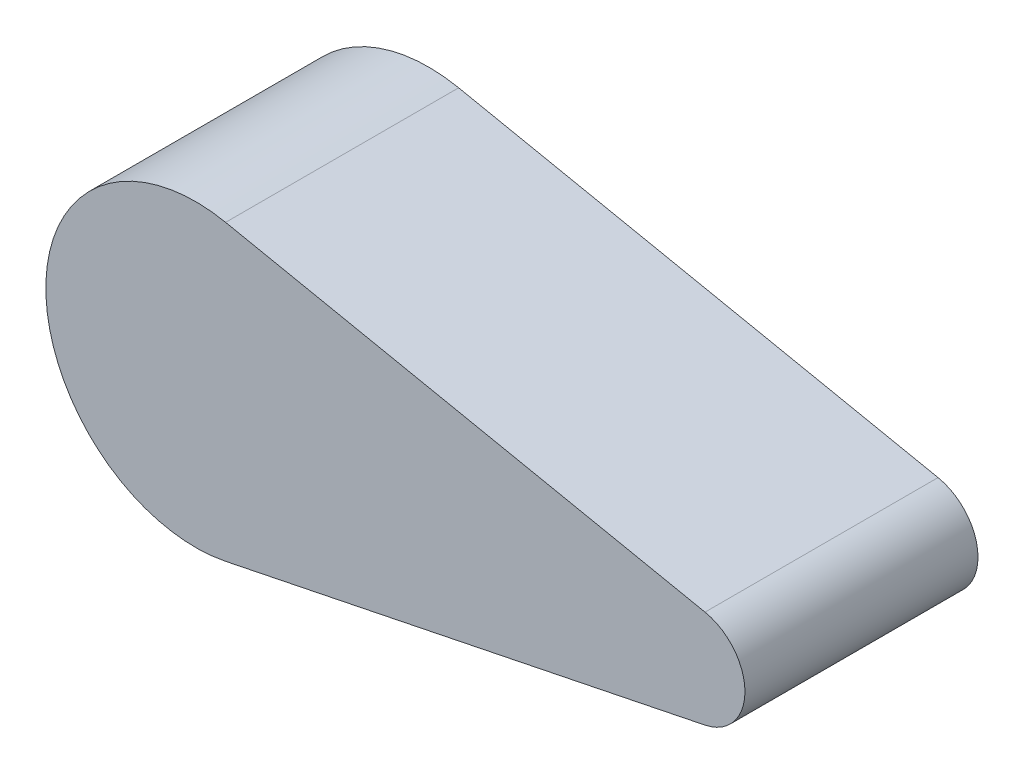
SolidWorks part; units mm, degrees
ref_plane "Front Plane" through (0, 0, 0) normal (0, 0, 1) x (1, 0, 0)
ref_plane "Top Plane" through (0, 0, 0) normal (0, 1, 0) x (1, 0, 0)
ref_plane "Right Plane" through (0, 0, 0) normal (1, 0, 0) x (0, 0, -1)
sketch "Sketch1" plane through (0, 0, 0) normal (0, 0, 1) x (1, 0, 0)
  line L0 (0, 0) -> (15, 0) construction
  line L1 (0.9, 4.4091) -> (15.3, 1.4697)
  line L2 (15.3, -1.4697) -> (0.9, -4.4091)
  arc A0 (0.9, 4.4091) -> (0.9, -4.4091) centre (0, 0) ccw
  arc A1 (15.3, -1.4697) -> (15.3, 1.4697) centre (15, 0) ccw
  dimension "D1" = 9
  dimension "D2" = 3
  dimension "D3" = 15
extrude "Boss-Extrude1" add sketch "Sketch1" along normal blind 7
sketch "Sketch2" plane through (0, 0, 0) normal (0, 0, -1) x (-1, 0, 0)
  line L20 (0.3236, -2.3303) -> (0.2859, -2.0671)
  line L21 (-0.4287, -2.0484) -> (-0.4802, -2.3093)
  line L22 (-1.1078, -2.087) -> (-0.9836, -1.8519)
  line L23 (-1.5507, -1.4168) -> (-1.7457, -1.5976)
  line L24 (-2.1228, -1.0489) -> (-1.8841, -0.9316)
  line L25 (-2.0871, -0.2463) -> (-2.3511, -0.2779)
  line L26 (-2.3337, 0.3876) -> (-2.0717, 0.3422)
  line L27 (-1.8331, 1.016) -> (-2.0653, 1.1456)
  line L28 (-1.66, 1.6737) -> (-1.4747, 1.483)
  line L29 (-0.8856, 1.8878) -> (-0.9973, 2.1292)
  line L30 (-0.359, 2.3182) -> (-0.3212, 2.055)
  line L31 (0.3934, 2.0363) -> (0.4449, 2.2972)
  line L32 (1.0724, 2.0749) -> (0.9483, 1.8398)
  line L33 (1.5153, 1.4047) -> (1.7103, 1.5854)
  line L34 (2.0874, 1.0368) -> (1.8488, 0.9195)
  line L35 (2.0518, 0.2342) -> (2.3158, 0.2658)
  line L36 (2.2983, -0.3997) -> (2.0363, -0.3543)
  line L37 (1.7977, -1.0281) -> (2.0299, -1.1577)
  line L38 (1.6246, -1.6858) -> (1.4394, -1.4951)
  line L39 (0.8503, -1.9) -> (0.962, -2.1413)
  line L40 (0.3236, -2.3303) -> (0.2859, -2.0671)
  line L41 (-0.4287, -2.0484) -> (-0.4802, -2.3093)
  line L42 (-1.1078, -2.087) -> (-0.9836, -1.8519)
  line L43 (-1.5507, -1.4168) -> (-1.7457, -1.5976)
  line L44 (-2.1228, -1.0489) -> (-1.8841, -0.9316)
  line L45 (-2.0871, -0.2463) -> (-2.3511, -0.2779)
  line L46 (-2.3337, 0.3876) -> (-2.0717, 0.3422)
  line L47 (-1.8331, 1.016) -> (-2.0653, 1.1456)
  line L48 (-1.66, 1.6737) -> (-1.4747, 1.483)
  line L49 (-0.8856, 1.8878) -> (-0.9973, 2.1292)
  line L50 (-0.359, 2.3182) -> (-0.3212, 2.055)
  line L51 (0.3934, 2.0363) -> (0.4449, 2.2972)
  line L52 (1.0724, 2.0749) -> (0.9483, 1.8398)
  line L53 (1.5153, 1.4047) -> (1.7103, 1.5854)
  line L54 (2.0874, 1.0368) -> (1.8488, 0.9195)
  line L55 (2.0518, 0.2342) -> (2.3158, 0.2658)
  line L56 (2.2983, -0.3997) -> (2.0363, -0.3543)
  line L57 (1.7977, -1.0281) -> (2.0299, -1.1577)
  line L58 (1.6246, -1.6858) -> (1.4394, -1.4951)
  line L59 (0.8503, -1.9) -> (0.962, -2.1413)
  arc A0 (-0.4287, -2.0484) -> (-0.5958, -1.7625) centre (-0.674, -2) ccw
  arc A1 (-0.6738, -1.7349) -> (-0.9836, -1.8519) centre (-0.7625, -1.9686) ccw
  arc A2 (-1.5507, -1.4168) -> (-1.5178, -1.0873) centre (-1.7206, -1.2334) ccw
  arc A3 (-1.5647, -1.0191) -> (-1.8841, -0.9316) centre (-1.7739, -1.156) ccw
  arc A4 (-2.0871, -0.2463) -> (-1.8669, 0.001) centre (-2.1169, 0.0019) ccw
  arc A5 (-1.8647, 0.0837) -> (-2.0717, 0.3422) centre (-2.1144, 0.0959) ccw
  arc A6 (-1.8331, 1.016) -> (-1.5095, 1.0866) centre (-1.7112, 1.2343) ccw
  arc A7 (-1.4592, 1.1522) -> (-1.4747, 1.483) centre (-1.654, 1.3088) ccw
  arc A8 (-0.8856, 1.8878) -> (-0.5824, 1.7548) centre (-0.6587, 1.9928) ccw
  arc A9 (-0.503, 1.7783) -> (-0.3212, 2.055) centre (-0.5687, 2.0195) ccw
  arc A10 (0.3934, 2.0363) -> (0.5605, 1.7504) centre (0.6386, 1.9879) ccw
  arc A11 (0.6385, 1.7228) -> (0.9483, 1.8398) centre (0.7272, 1.9565) ccw
  arc A12 (1.5153, 1.4047) -> (1.4825, 1.0752) centre (1.6853, 1.2213) ccw
  arc A13 (1.5294, 1.007) -> (1.8488, 0.9195) centre (1.7385, 1.1439) ccw
  arc A14 (2.0518, 0.2342) -> (1.8315, -0.0131) centre (2.0815, -0.0141) ccw
  arc A15 (1.8294, -0.0958) -> (2.0363, -0.3543) centre (2.0791, -0.108) ccw
  arc A16 (1.7977, -1.0281) -> (1.4742, -1.0987) centre (1.6759, -1.2464) ccw
  arc A17 (1.4238, -1.1643) -> (1.4394, -1.4951) centre (1.6187, -1.3209) ccw
  arc A18 (0.8503, -1.9) -> (0.5471, -1.7669) centre (0.6234, -2.005) ccw
  arc A19 (0.4677, -1.7904) -> (0.2859, -2.0671) centre (0.5333, -2.0316) ccw
  arc A20 (-0.4287, -2.0484) -> (-0.5958, -1.7625) centre (-0.674, -2) ccw
  arc A21 (-0.6738, -1.7349) -> (-0.9836, -1.8519) centre (-0.7625, -1.9686) ccw
  arc A22 (-1.5507, -1.4168) -> (-1.5178, -1.0873) centre (-1.7206, -1.2334) ccw
  arc A23 (-1.5647, -1.0191) -> (-1.8841, -0.9316) centre (-1.7739, -1.156) ccw
  arc A24 (-2.0871, -0.2463) -> (-1.8669, 0.001) centre (-2.1169, 0.0019) ccw
  arc A25 (-1.8647, 0.0837) -> (-2.0717, 0.3422) centre (-2.1144, 0.0959) ccw
  arc A26 (-1.8331, 1.016) -> (-1.5095, 1.0866) centre (-1.7112, 1.2343) ccw
  arc A27 (-1.4592, 1.1522) -> (-1.4747, 1.483) centre (-1.654, 1.3088) ccw
  arc A28 (-0.8856, 1.8878) -> (-0.5824, 1.7548) centre (-0.6587, 1.9928) ccw
  arc A29 (-0.503, 1.7783) -> (-0.3212, 2.055) centre (-0.5687, 2.0195) ccw
  arc A30 (0.3934, 2.0363) -> (0.5605, 1.7504) centre (0.6386, 1.9879) ccw
  arc A31 (0.6385, 1.7228) -> (0.9483, 1.8398) centre (0.7272, 1.9565) ccw
  arc A32 (1.5153, 1.4047) -> (1.4825, 1.0752) centre (1.6853, 1.2213) ccw
  arc A33 (1.5294, 1.007) -> (1.8488, 0.9195) centre (1.7385, 1.1439) ccw
  arc A34 (2.0518, 0.2342) -> (1.8315, -0.0131) centre (2.0815, -0.0141) ccw
  arc A35 (1.8294, -0.0958) -> (2.0363, -0.3543) centre (2.0791, -0.108) ccw
  arc A36 (1.7977, -1.0281) -> (1.4742, -1.0987) centre (1.6759, -1.2464) ccw
  arc A37 (1.4238, -1.1643) -> (1.4394, -1.4951) centre (1.6187, -1.3209) ccw
  arc A38 (0.8503, -1.9) -> (0.5471, -1.7669) centre (0.6234, -2.005) ccw
  arc A39 (0.4677, -1.7904) -> (0.2859, -2.0671) centre (0.5333, -2.0316) ccw
  ellipse E40 centre (-0.0177, -0.0061) end of major axis (-3.0095, -0.2276) minor radius 3 (-0.243, -2.9976) -> (0.0507, -3.0052) ccw
  ellipse E41 centre (-0.0177, -0.0061) end of major axis (-1.8618, -0.1426) minor radius 1.8492 (-0.6738, -1.7349) -> (-0.5958, -1.7625) ccw
  ellipse E42 centre (-0.0177, -0.0061) end of major axis (-3.0095, -0.2276) minor radius 3 (-1.9583, -2.2938) -> (-1.7253, -2.4726) ccw
  ellipse E43 centre (-0.0177, -0.0061) end of major axis (-1.8618, -0.1426) minor radius 1.8492 (-1.5647, -1.0191) -> (-1.5178, -1.0873) ccw
  ellipse E44 centre (-0.0177, -0.0061) end of major axis (-3.0095, -0.2276) minor radius 3 (-2.9324, -0.7162) -> (-2.849, -0.9979) ccw
  ellipse E45 centre (-0.0177, -0.0061) end of major axis (-1.8618, -0.1426) minor radius 1.8492 (-1.8647, 0.0837) -> (-1.8669, 0.001) ccw
  ellipse E46 centre (-0.0177, -0.0061) end of major axis (-3.0095, -0.2276) minor radius 3 (-2.7932, 1.1326) -> (-2.8912, 0.8557) ccw
  ellipse E47 centre (-0.0177, -0.0061) end of major axis (-1.8618, -0.1426) minor radius 1.8492 (-1.4592, 1.1522) -> (-1.5095, 1.0866) ccw
  ellipse E48 centre (-0.0177, -0.0061) end of major axis (-3.0095, -0.2276) minor radius 3 (-1.5938, 2.5465) -> (-1.8359, 2.3802) ccw
  ellipse E49 centre (-0.0177, -0.0061) end of major axis (-1.8618, -0.1426) minor radius 1.8492 (-0.503, 1.7783) -> (-0.5824, 1.7548) ccw
  ellipse E50 centre (-0.0177, -0.0061) end of major axis (-3.0095, -0.2276) minor radius 3 (0.2076, 2.9854) -> (-0.086, 2.9931) ccw
  ellipse E51 centre (-0.0177, -0.0061) end of major axis (-1.8618, -0.1426) minor radius 1.8492 (0.6385, 1.7228) -> (0.5605, 1.7504) ccw
  ellipse E52 centre (-0.0177, -0.0061) end of major axis (-3.0095, -0.2276) minor radius 3 (1.923, 2.2817) -> (1.6899, 2.4605) ccw
  ellipse E53 centre (-0.0177, -0.0061) end of major axis (-1.8618, -0.1426) minor radius 1.8492 (1.5294, 1.007) -> (1.4825, 1.0752) ccw
  ellipse E54 centre (-0.0177, -0.0061) end of major axis (-3.0095, -0.2276) minor radius 3 (2.8971, 0.7041) -> (2.8136, 0.9858) ccw
  ellipse E55 centre (-0.0177, -0.0061) end of major axis (-1.8618, -0.1426) minor radius 1.8492 (1.8294, -0.0958) -> (1.8315, -0.0131) ccw
  ellipse E56 centre (-0.0177, -0.0061) end of major axis (-3.0095, -0.2276) minor radius 3 (2.7578, -1.1447) -> (2.8559, -0.8679) ccw
  ellipse E57 centre (-0.0177, -0.0061) end of major axis (-1.8618, -0.1426) minor radius 1.8492 (1.4238, -1.1643) -> (1.4742, -1.0987) ccw
  ellipse E58 centre (-0.0177, -0.0061) end of major axis (-3.0095, -0.2276) minor radius 3 (1.5584, -2.5586) -> (1.8005, -2.3923) ccw
  ellipse E59 centre (-0.0177, -0.0061) end of major axis (-1.8618, -0.1426) minor radius 1.8492 (0.4677, -1.7904) -> (0.5471, -1.7669) ccw
  ellipse E60 centre (-0.0177, -0.0061) end of major axis (-3.0095, -0.2276) minor radius 3 (-0.243, -2.9976) -> (0.0507, -3.0052) ccw
  ellipse E61 centre (-0.0177, -0.0061) end of major axis (-1.8618, -0.1426) minor radius 1.8492 (-0.6738, -1.7349) -> (-0.5958, -1.7625) ccw
  ellipse E62 centre (-0.0177, -0.0061) end of major axis (-3.0095, -0.2276) minor radius 3 (-1.9583, -2.2938) -> (-1.7253, -2.4726) ccw
  ellipse E63 centre (-0.0177, -0.0061) end of major axis (-1.8618, -0.1426) minor radius 1.8492 (-1.5647, -1.0191) -> (-1.5178, -1.0873) ccw
  ellipse E64 centre (-0.0177, -0.0061) end of major axis (2.9741, 0.2155) minor radius 3 (-2.9324, -0.7162) -> (-2.849, -0.9979) ccw
  ellipse E65 centre (-0.0177, -0.0061) end of major axis (-1.8618, -0.1426) minor radius 1.8492 (-1.8647, 0.0837) -> (-1.8669, 0.001) ccw
  ellipse E66 centre (-0.0177, -0.0061) end of major axis (-3.0095, -0.2276) minor radius 3 (-2.7932, 1.1326) -> (-2.8912, 0.8557) ccw
  ellipse E67 centre (-0.0177, -0.0061) end of major axis (-1.8618, -0.1426) minor radius 1.8492 (-1.4592, 1.1522) -> (-1.5095, 1.0866) ccw
  ellipse E68 centre (-0.0177, -0.0061) end of major axis (2.9741, 0.2155) minor radius 3 (-1.5938, 2.5465) -> (-1.8359, 2.3802) ccw
  ellipse E69 centre (-0.0177, -0.0061) end of major axis (-1.8618, -0.1426) minor radius 1.8492 (-0.503, 1.7783) -> (-0.5824, 1.7548) ccw
  ellipse E70 centre (-0.0177, -0.0061) end of major axis (-3.0095, -0.2276) minor radius 3 (0.2076, 2.9854) -> (-0.086, 2.9931) ccw
  ellipse E71 centre (-0.0177, -0.0061) end of major axis (-1.8618, -0.1426) minor radius 1.8492 (0.6385, 1.7228) -> (0.5605, 1.7504) ccw
  ellipse E72 centre (-0.0177, -0.0061) end of major axis (2.9741, 0.2155) minor radius 3 (1.923, 2.2817) -> (1.6899, 2.4605) ccw
  ellipse E73 centre (-0.0177, -0.0061) end of major axis (-1.8618, -0.1426) minor radius 1.8492 (1.5294, 1.007) -> (1.4825, 1.0752) ccw
  ellipse E74 centre (-0.0177, -0.0061) end of major axis (2.9741, 0.2155) minor radius 3 (2.8971, 0.7041) -> (2.8136, 0.9858) ccw
  ellipse E75 centre (-0.0177, -0.0061) end of major axis (-1.8618, -0.1426) minor radius 1.8492 (1.8294, -0.0958) -> (1.8315, -0.0131) ccw
  ellipse E76 centre (-0.0177, -0.0061) end of major axis (-3.0095, -0.2276) minor radius 3 (2.7578, -1.1447) -> (2.8559, -0.8679) ccw
  ellipse E77 centre (-0.0177, -0.0061) end of major axis (-1.8618, -0.1426) minor radius 1.8492 (1.4238, -1.1643) -> (1.4742, -1.0987) ccw
  ellipse E78 centre (-0.0177, -0.0061) end of major axis (-3.0095, -0.2276) minor radius 3 (1.5584, -2.5586) -> (1.8005, -2.3923) ccw
  ellipse E79 centre (-0.0177, -0.0061) end of major axis (-1.8618, -0.1426) minor radius 1.8492 (0.4677, -1.7904) -> (0.5471, -1.7669) ccw
  spline S20 degree 5 poles (-1779.721, -915.2345) (7.6944, -3.6222) (-2.5035, -4.3059) (-1.1382, -4.0905) (-0.2415, -3.5081) (0.1702, -2.8271) (0.1999, -2.773) (0.226, -2.7206) (0.2478, -2.6719) (0.2651, -2.6289) (0.2798, -2.5879) (0.2923, -2.5488) (0.3031, -2.5097) (0.3107, -2.4766) (0.3176, -2.4416) (0.3448, -2.2239) (0.2959, -2.0224) (1.0633, -1.8322) (-50.4135, -4.4016) (1996.622, 113.6639) knots -4.645372 -4.645372 -4.645372 -4.645372 -4.645372 -4.645372 0.1 0.185714 0.271429 0.357143 0.428571 0.5 0.571429 0.628571 0.671429 0.728571 0.785714 0.857143 0.871429 0.928571 2.335849 2.335849 2.335849 2.335849 2.335849 2.335849 weights 1 1 1 1 1 1 1 1 1 1 1 1 1 1 1 1 1 1 1 1 only from (0.0507, -3.0052) to (0.3236, -2.3303)
  spline S21 degree 5 poles (-1988.254, 218.1058) (50.2637, -7.056) (0.2913, -1.9255) (-0.472, -1.9953) (-0.4918, -2.1948) (-0.4812, -2.4071) (-0.4779, -2.4364) (-0.4719, -2.4737) (-0.4646, -2.5112) (-0.4554, -2.5489) (-0.4414, -2.5986) (-0.4227, -2.6543) (-0.3994, -2.7141) (0.0409, -3.6972) (1.5023, -4.5925) (3.2962, -4.8306) (0.8271, 12.5308) (773.1993, -1847.274) knots -1.334982 -1.334982 -1.334982 -1.334982 -1.334982 -1.334982 0.071429 0.085714 0.142857 0.2 0.228571 0.285714 0.357143 0.414286 0.471429 0.585714 0.685714 0.785714 7.475131 7.475131 7.475131 7.475131 7.475131 7.475131 weights 1 1 1 1 1 1 1 1 1 1 1 1 1 1 1 1 1 1 only from (-0.4802, -2.3093) to (-0.243, -2.9976)
  spline S22 degree 5 poles (-1977.7891, 305.6323) (4.096, -7.4646) (-4.5562, -2.0236) (-3.3249, -2.6518) (-2.2572, -2.7077) (-1.5239, -2.3987) (-1.468, -2.3725) (-1.4161, -2.3454) (-1.3698, -2.3188) (-1.3306, -2.2942) (-1.2946, -2.2697) (-1.2615, -2.2454) (-1.2298, -2.2201) (-1.2042, -2.1977) (-1.178, -2.1735) (-1.0281, -2.0134) (-0.9492, -1.8216) (-0.2165, -2.1188) (-43.3724, 26.0595) (1682.1103, -1081.6302) knots -4.645372 -4.645372 -4.645372 -4.645372 -4.645372 -4.645372 0.1 0.185714 0.271429 0.357143 0.428571 0.5 0.571429 0.628571 0.671429 0.728571 0.785714 0.857143 0.871429 0.928571 2.335849 2.335849 2.335849 2.335849 2.335849 2.335849 weights 1 1 1 1 1 1 1 1 1 1 1 1 1 1 1 1 1 1 1 1 only from (-1.7253, -2.4726) to (-1.1078, -2.087)
  spline S23 degree 5 poles (-1480.3291, 1345.0962) (36.5169, -35.264) (-0.8959, -1.7405) (-1.5545, -1.3484) (-1.6878, -1.4981) (-1.804, -1.676) (-1.8185, -1.7017) (-1.8356, -1.7355) (-1.8518, -1.7701) (-1.8665, -1.8059) (-1.8843, -1.8544) (-1.9019, -1.9105) (-1.9183, -1.9725) (-2.1399, -3.0267) (-1.4839, -4.61) (-0.1725, -5.8571) (8.0348, 9.64) (-460.2792, -1948.9603) knots -1.334982 -1.334982 -1.334982 -1.334982 -1.334982 -1.334982 0.071429 0.085714 0.142857 0.2 0.228571 0.285714 0.357143 0.414286 0.471429 0.585714 0.685714 0.785714 7.475131 7.475131 7.475131 7.475131 7.475131 7.475131 weights 1 1 1 1 1 1 1 1 1 1 1 1 1 1 1 1 1 1 only from (-1.7457, -1.5976) to (-1.9583, -2.2938)
  spline S24 degree 5 poles (-1420.4288, 1409.7682) (-1.0737, -8.4581) (-4.8753, 1.0294) (-4.2485, -0.2026) (-3.4175, -0.8754) (-2.6426, -1.0565) (-2.582, -1.068) (-2.5241, -1.0767) (-2.471, -1.0823) (-2.4248, -1.0855) (-2.3812, -1.0868) (-2.3402, -1.0866) (-2.2997, -1.0848) (-2.2659, -1.0817) (-2.2304, -1.0776) (-2.015, -1.0361) (-1.8384, -0.9273) (-1.4204, -1.5984) (-19.7714, 46.5647) (725.0884, -1863.7945) knots -4.645381 -4.645381 -4.645381 -4.645381 -4.645381 -4.645381 0.1 0.185714 0.271429 0.357143 0.428571 0.5 0.571429 0.628571 0.671429 0.728571 0.785714 0.857143 0.871429 0.928571 2.335851 2.335851 2.335851 2.335851 2.335851 2.335851 weights 1 1 1 1 1 1 1 1 1 1 1 1 1 1 1 1 1 1 1 1 only from (-2.849, -0.9979) to (-2.1228, -1.0489)
  spline S25 degree 5 poles (-406.9751, 1958.3014) (8.8151, -50.0046) (-1.7477, -0.8931) (-2.05, -0.1887) (-2.2458, -0.2315) (-2.4444, -0.3071) (-2.4713, -0.3194) (-2.505, -0.3366) (-2.5384, -0.3551) (-2.5714, -0.3755) (-2.6143, -0.4042) (-2.6615, -0.4393) (-2.7112, -0.4798) (-3.5101, -1.2024) (-3.91, -2.8689) (-3.5821, -4.6486) (12.1666, 3.0646) (-1517.9385, -1306.2002) knots -1.334982 -1.334982 -1.334982 -1.334982 -1.334982 -1.334982 0.071429 0.085714 0.142857 0.2 0.228571 0.285714 0.357143 0.414286 0.471429 0.585714 0.685714 0.785714 7.475118 7.475118 7.475118 7.475118 7.475118 7.475118 weights 1 1 1 1 1 1 1 1 1 1 1 1 1 1 1 1 1 1 only from (-2.3511, -0.2779) to (-2.9324, -0.7162)
  spline S26 degree 5 poles (-320.5015, 1975.416) (-5.8401, -6.2232) (-3.3389, 3.6869) (-3.556, 2.3217) (-3.2792, 1.289) (-2.7587, 0.687) (-2.7165, 0.6421) (-2.6747, 0.601) (-2.6351, 0.5652) (-2.5996, 0.5355) (-2.5651, 0.5088) (-2.5318, 0.4849) (-2.498, 0.4625) (-2.4688, 0.4451) (-2.4376, 0.4277) (-2.239, 0.3346) (-2.0322, 0.3188) (-2.0884, -0.4698) (11.3751, 49.2814) (-508.912, -1934.047) knots -4.645381 -4.645381 -4.645381 -4.645381 -4.645381 -4.645381 0.1 0.185714 0.271429 0.357143 0.428571 0.5 0.571429 0.628571 0.671429 0.728571 0.785714 0.857143 0.871429 0.928571 2.335851 2.335851 2.335851 2.335851 2.335851 2.335851 weights 1 1 1 1 1 1 1 1 1 1 1 1 1 1 1 1 1 1 1 1 only from (-2.8912, 0.8557) to (-2.3337, 0.3876)
  spline S27 degree 5 poles (821.8214, 1823.5009) (-22.2605, -45.6475) (-1.9387, 0.2932) (-1.7692, 1.0407) (-1.9528, 1.1212) (-2.1579, 1.1768) (-2.1868, 1.1826) (-2.2242, 1.1885) (-2.2621, 1.1931) (-2.3008, 1.1961) (-2.3524, 1.198) (-2.4112, 1.1975) (-2.4752, 1.1938) (-3.5463, 1.0788) (-4.8494, -0.0343) (-5.6302, -1.6669) (11.6445, -4.6835) (-1995.8088, -164.5365) knots -1.334982 -1.334982 -1.334982 -1.334982 -1.334982 -1.334982 0.071429 0.085714 0.142857 0.2 0.228571 0.285714 0.357143 0.414286 0.471429 0.585714 0.685714 0.785714 7.475118 7.475118 7.475118 7.475118 7.475118 7.475118 weights 1 1 1 1 1 1 1 1 1 1 1 1 1 1 1 1 1 1 only from (-2.0653, 1.1456) to (-2.7932, 1.1326)
  spline S28 degree 5 poles (901.8398, 1786.5194) (-8.3825, -1.6136) (-0.5339, 4.9337) (-1.512, 3.9569) (-1.8951, 2.9587) (-1.8278, 2.1658) (-1.8201, 2.1046) (-1.8104, 2.0468) (-1.7994, 1.9946) (-1.7882, 1.9497) (-1.7759, 1.9078) (-1.7631, 1.8688) (-1.7488, 1.8309) (-1.7354, 1.7997) (-1.7205, 1.7673) (-1.6145, 1.5752) (-1.4565, 1.4409) (-1.9655, 0.8359) (38.17, 33.1719) (-1548.532, -1265.5615) knots -4.645381 -4.645381 -4.645381 -4.645381 -4.645381 -4.645381 0.1 0.185714 0.271429 0.357143 0.428571 0.5 0.571429 0.628571 0.671429 0.728571 0.785714 0.857143 0.871429 0.928571 2.335851 2.335851 2.335851 2.335851 2.335851 2.335851 weights 1 1 1 1 1 1 1 1 1 1 1 1 1 1 1 1 1 1 1 1 only from (-1.8359, 2.3802) to (-1.66, 1.6737)
  spline S29 degree 5 poles (1736.7033, 992.1828) (-44.84, -23.8569) (-1.3959, 1.3652) (-0.8194, 1.8703) (-0.9206, 2.0434) (-1.0539, 2.2089) (-1.0739, 2.2306) (-1.1007, 2.2573) (-1.1286, 2.2834) (-1.1582, 2.3085) (-1.1987, 2.3404) (-1.2467, 2.3745) (-1.3006, 2.4092) (-2.2347, 2.9457) (-3.9432, 2.8111) (-5.5345, 1.9493) (6.6679, -10.645) (-1711.3543, 1039.9724) knots -1.334982 -1.334982 -1.334982 -1.334982 -1.334982 -1.334982 0.071429 0.085714 0.142857 0.2 0.228571 0.285714 0.357143 0.414286 0.471429 0.585714 0.685714 0.785714 7.475118 7.475118 7.475118 7.475118 7.475118 7.475118 weights 1 1 1 1 1 1 1 1 1 1 1 1 1 1 1 1 1 1 only from (-0.9973, 2.1292) to (-1.5938, 2.5465)
  spline S30 degree 5 poles (1779.6857, 915.2225) (-7.7297, 3.6101) (2.4682, 4.2938) (1.1028, 4.0784) (0.2061, 3.496) (-0.2055, 2.815) (-0.2352, 2.7609) (-0.2614, 2.7085) (-0.2832, 2.6598) (-0.3005, 2.6168) (-0.3152, 2.5758) (-0.3277, 2.5367) (-0.3385, 2.4976) (-0.346, 2.4645) (-0.353, 2.4295) (-0.3801, 2.2118) (-0.3312, 2.0103) (-1.0986, 1.82) (50.3781, 4.3895) (-1996.6573, -113.676) knots -4.645372 -4.645372 -4.645372 -4.645372 -4.645372 -4.645372 0.1 0.185714 0.271429 0.357143 0.428571 0.5 0.571429 0.628571 0.671429 0.728571 0.785714 0.857143 0.871429 0.928571 2.335849 2.335849 2.335849 2.335849 2.335849 2.335849 weights 1 1 1 1 1 1 1 1 1 1 1 1 1 1 1 1 1 1 1 1 only from (-0.086, 2.9931) to (-0.359, 2.3182)
  spline S31 degree 5 poles (1988.2187, -218.1179) (-50.299, 7.0439) (-0.3267, 1.9134) (0.4366, 1.9832) (0.4565, 2.1827) (0.4459, 2.3949) (0.4425, 2.4243) (0.4366, 2.4616) (0.4293, 2.4991) (0.4201, 2.5368) (0.406, 2.5865) (0.3873, 2.6422) (0.3641, 2.702) (-0.0762, 3.6851) (-1.5376, 4.5804) (-3.3316, 4.8185) (-0.8624, -12.5429) (-773.2347, 1847.2619) knots -1.334982 -1.334982 -1.334982 -1.334982 -1.334982 -1.334982 0.071429 0.085714 0.142857 0.2 0.228571 0.285714 0.357143 0.414286 0.471429 0.585714 0.685714 0.785714 7.475131 7.475131 7.475131 7.475131 7.475131 7.475131 weights 1 1 1 1 1 1 1 1 1 1 1 1 1 1 1 1 1 1 only from (0.4449, 2.2972) to (0.2076, 2.9854)
  spline S32 degree 5 poles (1977.7538, -305.6444) (-4.1313, 7.4525) (4.5209, 2.0114) (3.2896, 2.6397) (2.2219, 2.6956) (1.4885, 2.3866) (1.4327, 2.3604) (1.3808, 2.3333) (1.3345, 2.3067) (1.2952, 2.2821) (1.2592, 2.2576) (1.2261, 2.2333) (1.1944, 2.208) (1.1689, 2.1856) (1.1427, 2.1614) (0.9927, 2.0013) (0.9139, 1.8095) (0.1812, 2.1066) (43.337, -26.0716) (-1682.1456, 1081.6181) knots -4.645372 -4.645372 -4.645372 -4.645372 -4.645372 -4.645372 0.1 0.185714 0.271429 0.357143 0.428571 0.5 0.571429 0.628571 0.671429 0.728571 0.785714 0.857143 0.871429 0.928571 2.335849 2.335849 2.335849 2.335849 2.335849 2.335849 weights 1 1 1 1 1 1 1 1 1 1 1 1 1 1 1 1 1 1 1 1 only from (1.6899, 2.4605) to (1.0724, 2.0749)
  spline S33 degree 5 poles (1480.2937, -1345.1083) (-36.5522, 35.2519) (0.8606, 1.7284) (1.5191, 1.3363) (1.6524, 1.486) (1.7687, 1.6639) (1.7832, 1.6896) (1.8003, 1.7233) (1.8164, 1.758) (1.8312, 1.7938) (1.849, 1.8423) (1.8666, 1.8984) (1.8829, 1.9604) (2.1045, 3.0146) (1.4486, 4.5979) (0.1372, 5.8449) (-8.0702, -9.6521) (460.244, 1948.9481) knots -1.334982 -1.334982 -1.334982 -1.334982 -1.334982 -1.334982 0.071429 0.085714 0.142857 0.2 0.228571 0.285714 0.357143 0.414286 0.471429 0.585714 0.685714 0.785714 7.475131 7.475131 7.475131 7.475131 7.475131 7.475131 weights 1 1 1 1 1 1 1 1 1 1 1 1 1 1 1 1 1 1 only from (1.7103, 1.5854) to (1.923, 2.2817)
  spline S34 degree 5 poles (1420.3936, -1409.7804) (1.0384, 8.446) (4.8399, -1.0415) (4.2131, 0.1905) (3.3822, 0.8633) (2.6073, 1.0444) (2.5467, 1.0559) (2.4887, 1.0646) (2.4357, 1.0702) (2.3895, 1.0734) (2.3459, 1.0747) (2.3048, 1.0745) (2.2644, 1.0727) (2.2305, 1.0696) (2.1951, 1.0654) (1.9796, 1.024) (1.8031, 0.9152) (1.385, 1.5863) (19.736, -46.5768) (-725.1237, 1863.7824) knots -4.645381 -4.645381 -4.645381 -4.645381 -4.645381 -4.645381 0.1 0.185714 0.271429 0.357143 0.428571 0.5 0.571429 0.628571 0.671429 0.728571 0.785714 0.857143 0.871429 0.928571 2.335851 2.335851 2.335851 2.335851 2.335851 2.335851 weights 1 1 1 1 1 1 1 1 1 1 1 1 1 1 1 1 1 1 1 1 only from (2.8136, 0.9858) to (2.0874, 1.0368)
  spline S35 degree 5 poles (406.9398, -1958.3135) (-8.8504, 49.9925) (1.7123, 0.881) (2.0146, 0.1766) (2.2105, 0.2194) (2.4091, 0.295) (2.4359, 0.3073) (2.4696, 0.3245) (2.503, 0.343) (2.536, 0.3634) (2.5789, 0.3921) (2.6262, 0.4271) (2.6758, 0.4677) (3.4747, 1.1903) (3.8747, 2.8568) (3.5468, 4.6365) (-12.202, -3.0767) (1517.9032, 1306.1881) knots -1.334982 -1.334982 -1.334982 -1.334982 -1.334982 -1.334982 0.071429 0.085714 0.142857 0.2 0.228571 0.285714 0.357143 0.414286 0.471429 0.585714 0.685714 0.785714 7.475118 7.475118 7.475118 7.475118 7.475118 7.475118 weights 1 1 1 1 1 1 1 1 1 1 1 1 1 1 1 1 1 1 only from (2.3158, 0.2658) to (2.8971, 0.7041)
  spline S36 degree 5 poles (320.4662, -1975.4281) (5.8047, 6.2111) (3.3036, -3.699) (3.5206, -2.3338) (3.2439, -1.3011) (2.7234, -0.6991) (2.6811, -0.6542) (2.6394, -0.6131) (2.5998, -0.5773) (2.5642, -0.5476) (2.5297, -0.5209) (2.4964, -0.497) (2.4626, -0.4746) (2.4334, -0.4572) (2.4023, -0.4398) (2.2036, -0.3467) (1.9969, -0.3309) (2.0531, 0.4577) (-11.4105, -49.2935) (508.8767, 1934.0349) knots -4.645381 -4.645381 -4.645381 -4.645381 -4.645381 -4.645381 0.1 0.185714 0.271429 0.357143 0.428571 0.5 0.571429 0.628571 0.671429 0.728571 0.785714 0.857143 0.871429 0.928571 2.335851 2.335851 2.335851 2.335851 2.335851 2.335851 weights 1 1 1 1 1 1 1 1 1 1 1 1 1 1 1 1 1 1 1 1 only from (2.8559, -0.8679) to (2.2983, -0.3997)
  spline S37 degree 5 poles (-821.8567, -1823.5131) (22.2251, 45.6354) (1.9033, -0.3053) (1.7339, -1.0528) (1.9174, -1.1333) (2.1226, -1.1889) (2.1515, -1.1947) (2.1889, -1.2006) (2.2268, -1.2052) (2.2655, -1.2082) (2.3171, -1.2102) (2.3759, -1.2096) (2.4399, -1.206) (3.5109, -1.091) (4.8141, 0.0222) (5.5949, 1.6548) (-11.6799, 4.6714) (1995.7734, 164.5244) knots -1.334982 -1.334982 -1.334982 -1.334982 -1.334982 -1.334982 0.071429 0.085714 0.142857 0.2 0.228571 0.285714 0.357143 0.414286 0.471429 0.585714 0.685714 0.785714 7.475118 7.475118 7.475118 7.475118 7.475118 7.475118 weights 1 1 1 1 1 1 1 1 1 1 1 1 1 1 1 1 1 1 only from (2.0299, -1.1577) to (2.7578, -1.1447)
  spline S38 degree 5 poles (-901.8752, -1786.5315) (8.3471, 1.6015) (0.4986, -4.9459) (1.4766, -3.969) (1.8598, -2.9708) (1.7925, -2.1779) (1.7847, -2.1167) (1.7751, -2.0589) (1.7641, -2.0067) (1.7528, -1.9618) (1.7406, -1.9199) (1.7277, -1.881) (1.7135, -1.843) (1.7001, -1.8118) (1.6852, -1.7794) (1.5792, -1.5873) (1.4212, -1.453) (1.9302, -0.8481) (-38.2053, -33.184) (1548.4967, 1265.5494) knots -4.645381 -4.645381 -4.645381 -4.645381 -4.645381 -4.645381 0.1 0.185714 0.271429 0.357143 0.428571 0.5 0.571429 0.628571 0.671429 0.728571 0.785714 0.857143 0.871429 0.928571 2.335851 2.335851 2.335851 2.335851 2.335851 2.335851 weights 1 1 1 1 1 1 1 1 1 1 1 1 1 1 1 1 1 1 1 1 only from (1.8005, -2.3923) to (1.6246, -1.6858)
  spline S39 degree 5 poles (-1736.7386, -992.1949) (44.8047, 23.8448) (1.3605, -1.3773) (0.7841, -1.8824) (0.8853, -2.0555) (1.0186, -2.221) (1.0385, -2.2427) (1.0653, -2.2694) (1.0933, -2.2955) (1.1228, -2.3206) (1.1634, -2.3525) (1.2113, -2.3866) (1.2652, -2.4213) (2.1993, -2.9578) (3.9079, -2.8232) (5.4992, -1.9614) (-6.7032, 10.6329) (1711.3191, -1039.9845) knots -1.334982 -1.334982 -1.334982 -1.334982 -1.334982 -1.334982 0.071429 0.085714 0.142857 0.2 0.228571 0.285714 0.357143 0.414286 0.471429 0.585714 0.685714 0.785714 7.475118 7.475118 7.475118 7.475118 7.475118 7.475118 weights 1 1 1 1 1 1 1 1 1 1 1 1 1 1 1 1 1 1 only from (0.962, -2.1413) to (1.5584, -2.5586)
  spline S40 degree 5 poles (0.0507, -3.0052) (0.0606, -2.9922) (0.0786, -2.9679) (0.1039, -2.9321) (0.1354, -2.8846) (0.1702, -2.8271) (0.1999, -2.773) (0.226, -2.7206) (0.2478, -2.6719) (0.2651, -2.6289) (0.2798, -2.5879) (0.2923, -2.5488) (0.3031, -2.5097) (0.3107, -2.4766) (0.3176, -2.4416) (0.3222, -2.4048) (0.3244, -2.376) (0.326, -2.3568) (0.325, -2.3397) (0.3236, -2.3303) knots 0 0 0 0 0 0 0.1 0.185714 0.271429 0.357143 0.428571 0.5 0.571429 0.628571 0.671429 0.728571 0.785714 0.857143 0.871429 0.928571 1 1 1 1 1 1 weights 1 1 1 1 1 1 1 1 1 1 1 1 1 1 1 1 1 1 1 1
  spline S41 degree 5 poles (-0.4802, -2.3093) (-0.482, -2.3186) (-0.4833, -2.3299) (-0.4836, -2.349) (-0.4828, -2.376) (-0.4812, -2.4071) (-0.4779, -2.4364) (-0.4719, -2.4737) (-0.4646, -2.5112) (-0.4554, -2.5489) (-0.4414, -2.5986) (-0.4227, -2.6543) (-0.3994, -2.7141) (-0.3629, -2.7956) (-0.3241, -2.8688) (-0.2902, -2.9257) (-0.2627, -2.9685) (-0.243, -2.9976) knots 0 0 0 0 0 0 0.071429 0.085714 0.142857 0.2 0.228571 0.285714 0.357143 0.414286 0.471429 0.585714 0.685714 0.785714 1 1 1 1 1 1 weights 1 1 1 1 1 1 1 1 1 1 1 1 1 1 1 1 1 1
  spline S42 degree 5 poles (-1.7253, -2.4726) (-1.7096, -2.4679) (-1.6807, -2.4588) (-1.6392, -2.4448) (-1.5858, -2.4248) (-1.5239, -2.3987) (-1.468, -2.3725) (-1.4161, -2.3454) (-1.3698, -2.3188) (-1.3306, -2.2942) (-1.2946, -2.2697) (-1.2615, -2.2454) (-1.2298, -2.2201) (-1.2042, -2.1977) (-1.178, -2.1735) (-1.1527, -2.1465) (-1.1339, -2.1244) (-1.1214, -2.1098) (-1.1122, -2.0954) (-1.1078, -2.087) knots 0 0 0 0 0 0 0.1 0.185714 0.271429 0.357143 0.428571 0.5 0.571429 0.628571 0.671429 0.728571 0.785714 0.857143 0.871429 0.928571 1 1 1 1 1 1 weights 1 1 1 1 1 1 1 1 1 1 1 1 1 1 1 1 1 1 1 1
  spline S43 degree 5 poles (-1.7457, -1.5976) (-1.7526, -1.604) (-1.7603, -1.6124) (-1.7718, -1.6277) (-1.787, -1.65) (-1.804, -1.676) (-1.8185, -1.7017) (-1.8356, -1.7355) (-1.8518, -1.7701) (-1.8665, -1.8059) (-1.8843, -1.8544) (-1.9019, -1.9105) (-1.9183, -1.9725) (-1.9367, -2.06) (-1.9483, -2.1419) (-1.9543, -2.2079) (-1.9572, -2.2587) (-1.9583, -2.2938) knots 0 0 0 0 0 0 0.071429 0.085714 0.142857 0.2 0.228571 0.285714 0.357143 0.414286 0.471429 0.585714 0.685714 0.785714 1 1 1 1 1 1 weights 1 1 1 1 1 1 1 1 1 1 1 1 1 1 1 1 1 1
  spline S44 degree 5 poles (-2.849, -0.9979) (-2.8335, -1.0032) (-2.8048, -1.0128) (-2.7629, -1.0259) (-2.7081, -1.0412) (-2.6426, -1.0565) (-2.582, -1.068) (-2.5241, -1.0767) (-2.471, -1.0823) (-2.4248, -1.0855) (-2.3812, -1.0868) (-2.3402, -1.0866) (-2.2997, -1.0848) (-2.2659, -1.0817) (-2.2304, -1.0776) (-2.194, -1.0706) (-2.1659, -1.0637) (-2.1472, -1.0593) (-2.1313, -1.0531) (-2.1228, -1.0489) knots 0 0 0 0 0 0 0.1 0.185714 0.271429 0.357143 0.428571 0.5 0.571429 0.628571 0.671429 0.728571 0.785714 0.857143 0.871429 0.928571 1 1 1 1 1 1 weights 1 1 1 1 1 1 1 1 1 1 1 1 1 1 1 1 1 1 1 1
  spline S45 degree 5 poles (-2.3511, -0.2779) (-2.3605, -0.279) (-2.3717, -0.2813) (-2.39, -0.2869) (-2.4154, -0.2961) (-2.4444, -0.3071) (-2.4713, -0.3194) (-2.505, -0.3366) (-2.5384, -0.3551) (-2.5714, -0.3755) (-2.6143, -0.4042) (-2.6615, -0.4393) (-2.7112, -0.4798) (-2.7774, -0.5398) (-2.835, -0.5993) (-2.8787, -0.649) (-2.9109, -0.6885) (-2.9324, -0.7162) knots 0 0 0 0 0 0 0.071429 0.085714 0.142857 0.2 0.228571 0.285714 0.357143 0.414286 0.471429 0.585714 0.685714 0.785714 1 1 1 1 1 1 weights 1 1 1 1 1 1 1 1 1 1 1 1 1 1 1 1 1 1
  spline S46 degree 5 poles (-2.8912, 0.8557) (-2.8819, 0.8423) (-2.8643, 0.8177) (-2.8381, 0.7825) (-2.8027, 0.7379) (-2.7587, 0.687) (-2.7165, 0.6421) (-2.6747, 0.601) (-2.6351, 0.5652) (-2.5996, 0.5355) (-2.5651, 0.5088) (-2.5318, 0.4849) (-2.498, 0.4625) (-2.4688, 0.4451) (-2.4376, 0.4277) (-2.4041, 0.412) (-2.3773, 0.401) (-2.3596, 0.3935) (-2.343, 0.3892) (-2.3337, 0.3876) knots 0 0 0 0 0 0 0.1 0.185714 0.271429 0.357143 0.428571 0.5 0.571429 0.628571 0.671429 0.728571 0.785714 0.857143 0.871429 0.928571 1 1 1 1 1 1 weights 1 1 1 1 1 1 1 1 1 1 1 1 1 1 1 1 1 1 1 1
  spline S47 degree 5 poles (-2.0653, 1.1456) (-2.0736, 1.1502) (-2.0839, 1.1549) (-2.102, 1.1611) (-2.1279, 1.1687) (-2.1579, 1.1768) (-2.1868, 1.1826) (-2.2242, 1.1885) (-2.2621, 1.1931) (-2.3008, 1.1961) (-2.3524, 1.198) (-2.4112, 1.1975) (-2.4752, 1.1938) (-2.5641, 1.1843) (-2.6456, 1.17) (-2.7102, 1.1554) (-2.7595, 1.1424) (-2.7932, 1.1326) knots 0 0 0 0 0 0 0.071429 0.085714 0.142857 0.2 0.228571 0.285714 0.357143 0.414286 0.471429 0.585714 0.685714 0.785714 1 1 1 1 1 1 weights 1 1 1 1 1 1 1 1 1 1 1 1 1 1 1 1 1 1
  spline S48 degree 5 poles (-1.8359, 2.3802) (-1.8362, 2.3638) (-1.8365, 2.3335) (-1.836, 2.2897) (-1.8335, 2.2328) (-1.8278, 2.1658) (-1.8201, 2.1046) (-1.8104, 2.0468) (-1.7994, 1.9946) (-1.7882, 1.9497) (-1.7759, 1.9078) (-1.7631, 1.8688) (-1.7488, 1.8309) (-1.7354, 1.7997) (-1.7205, 1.7673) (-1.7026, 1.7348) (-1.6874, 1.7102) (-1.6774, 1.6937) (-1.6666, 1.6805) (-1.66, 1.6737) knots 0 0 0 0 0 0 0.1 0.185714 0.271429 0.357143 0.428571 0.5 0.571429 0.628571 0.671429 0.728571 0.785714 0.857143 0.871429 0.928571 1 1 1 1 1 1 weights 1 1 1 1 1 1 1 1 1 1 1 1 1 1 1 1 1 1 1 1
  spline S49 degree 5 poles (-0.9973, 2.1292) (-1.0013, 2.1378) (-1.0069, 2.1477) (-1.0179, 2.1633) (-1.0344, 2.1847) (-1.0539, 2.2089) (-1.0739, 2.2306) (-1.1007, 2.2573) (-1.1286, 2.2834) (-1.1582, 2.3085) (-1.1987, 2.3404) (-1.2467, 2.3745) (-1.3006, 2.4092) (-1.3781, 2.4537) (-1.4524, 2.49) (-1.5133, 2.5162) (-1.5608, 2.5346) (-1.5938, 2.5465) knots 0 0 0 0 0 0 0.071429 0.085714 0.142857 0.2 0.228571 0.285714 0.357143 0.414286 0.471429 0.585714 0.685714 0.785714 1 1 1 1 1 1 weights 1 1 1 1 1 1 1 1 1 1 1 1 1 1 1 1 1 1
  spline S50 degree 5 poles (-0.086, 2.9931) (-0.0959, 2.9801) (-0.1139, 2.9558) (-0.1393, 2.92) (-0.1708, 2.8725) (-0.2055, 2.815) (-0.2352, 2.7609) (-0.2614, 2.7085) (-0.2832, 2.6598) (-0.3005, 2.6168) (-0.3152, 2.5758) (-0.3277, 2.5367) (-0.3385, 2.4976) (-0.346, 2.4645) (-0.353, 2.4295) (-0.3575, 2.3927) (-0.3597, 2.3639) (-0.3613, 2.3447) (-0.3603, 2.3276) (-0.359, 2.3182) knots 0 0 0 0 0 0 0.1 0.185714 0.271429 0.357143 0.428571 0.5 0.571429 0.628571 0.671429 0.728571 0.785714 0.857143 0.871429 0.928571 1 1 1 1 1 1 weights 1 1 1 1 1 1 1 1 1 1 1 1 1 1 1 1 1 1 1 1
  spline S51 degree 5 poles (0.4449, 2.2972) (0.4467, 2.3065) (0.448, 2.3178) (0.4483, 2.3369) (0.4474, 2.3639) (0.4459, 2.3949) (0.4425, 2.4243) (0.4366, 2.4616) (0.4293, 2.4991) (0.4201, 2.5368) (0.406, 2.5865) (0.3873, 2.6422) (0.3641, 2.702) (0.3276, 2.7835) (0.2888, 2.8567) (0.2549, 2.9136) (0.2273, 2.9564) (0.2076, 2.9854) knots 0 0 0 0 0 0 0.071429 0.085714 0.142857 0.2 0.228571 0.285714 0.357143 0.414286 0.471429 0.585714 0.685714 0.785714 1 1 1 1 1 1 weights 1 1 1 1 1 1 1 1 1 1 1 1 1 1 1 1 1 1
  spline S52 degree 5 poles (1.6899, 2.4605) (1.6743, 2.4558) (1.6454, 2.4467) (1.6038, 2.4327) (1.5505, 2.4127) (1.4885, 2.3866) (1.4327, 2.3604) (1.3808, 2.3333) (1.3345, 2.3067) (1.2952, 2.2821) (1.2592, 2.2576) (1.2261, 2.2333) (1.1944, 2.208) (1.1689, 2.1856) (1.1427, 2.1614) (1.1173, 2.1344) (1.0986, 2.1123) (1.086, 2.0977) (1.0769, 2.0833) (1.0724, 2.0749) knots 0 0 0 0 0 0 0.1 0.185714 0.271429 0.357143 0.428571 0.5 0.571429 0.628571 0.671429 0.728571 0.785714 0.857143 0.871429 0.928571 1 1 1 1 1 1 weights 1 1 1 1 1 1 1 1 1 1 1 1 1 1 1 1 1 1 1 1
  spline S53 degree 5 poles (1.7103, 1.5854) (1.7173, 1.5919) (1.725, 1.6003) (1.7365, 1.6156) (1.7517, 1.6379) (1.7687, 1.6639) (1.7832, 1.6896) (1.8003, 1.7233) (1.8164, 1.758) (1.8312, 1.7938) (1.849, 1.8423) (1.8666, 1.8984) (1.8829, 1.9604) (1.9013, 2.0478) (1.9129, 2.1298) (1.919, 2.1958) (1.9218, 2.2466) (1.923, 2.2817) knots 0 0 0 0 0 0 0.071429 0.085714 0.142857 0.2 0.228571 0.285714 0.357143 0.414286 0.471429 0.585714 0.685714 0.785714 1 1 1 1 1 1 weights 1 1 1 1 1 1 1 1 1 1 1 1 1 1 1 1 1 1
  spline S54 degree 5 poles (2.8136, 0.9858) (2.7982, 0.9911) (2.7695, 1.0007) (2.7276, 1.0138) (2.6727, 1.0291) (2.6073, 1.0444) (2.5467, 1.0559) (2.4887, 1.0646) (2.4357, 1.0702) (2.3895, 1.0734) (2.3459, 1.0747) (2.3048, 1.0745) (2.2644, 1.0727) (2.2305, 1.0696) (2.1951, 1.0654) (2.1587, 1.0584) (2.1306, 1.0516) (2.1118, 1.0472) (2.0959, 1.041) (2.0874, 1.0368) knots 0 0 0 0 0 0 0.1 0.185714 0.271429 0.357143 0.428571 0.5 0.571429 0.628571 0.671429 0.728571 0.785714 0.857143 0.871429 0.928571 1 1 1 1 1 1 weights 1 1 1 1 1 1 1 1 1 1 1 1 1 1 1 1 1 1 1 1
  spline S55 degree 5 poles (2.3158, 0.2658) (2.3252, 0.2669) (2.3364, 0.2692) (2.3546, 0.2748) (2.3801, 0.284) (2.4091, 0.295) (2.4359, 0.3073) (2.4696, 0.3245) (2.503, 0.343) (2.536, 0.3634) (2.5789, 0.3921) (2.6262, 0.4271) (2.6758, 0.4677) (2.7421, 0.5276) (2.7997, 0.5871) (2.8433, 0.6369) (2.8755, 0.6764) (2.8971, 0.7041) knots 0 0 0 0 0 0 0.071429 0.085714 0.142857 0.2 0.228571 0.285714 0.357143 0.414286 0.471429 0.585714 0.685714 0.785714 1 1 1 1 1 1 weights 1 1 1 1 1 1 1 1 1 1 1 1 1 1 1 1 1 1
  spline S56 degree 5 poles (2.8559, -0.8679) (2.8465, -0.8544) (2.829, -0.8298) (2.8028, -0.7946) (2.7673, -0.75) (2.7234, -0.6991) (2.6811, -0.6542) (2.6394, -0.6131) (2.5998, -0.5773) (2.5642, -0.5476) (2.5297, -0.5209) (2.4964, -0.497) (2.4626, -0.4746) (2.4334, -0.4572) (2.4023, -0.4398) (2.3687, -0.4241) (2.342, -0.4131) (2.3242, -0.4056) (2.3077, -0.4013) (2.2983, -0.3997) knots 0 0 0 0 0 0 0.1 0.185714 0.271429 0.357143 0.428571 0.5 0.571429 0.628571 0.671429 0.728571 0.785714 0.857143 0.871429 0.928571 1 1 1 1 1 1 weights 1 1 1 1 1 1 1 1 1 1 1 1 1 1 1 1 1 1 1 1
  spline S57 degree 5 poles (2.0299, -1.1577) (2.0382, -1.1623) (2.0486, -1.167) (2.0667, -1.1732) (2.0926, -1.1808) (2.1226, -1.1889) (2.1515, -1.1947) (2.1889, -1.2006) (2.2268, -1.2052) (2.2655, -1.2082) (2.3171, -1.2102) (2.3759, -1.2096) (2.4399, -1.206) (2.5287, -1.1964) (2.6103, -1.1821) (2.6749, -1.1675) (2.7241, -1.1545) (2.7578, -1.1447) knots 0 0 0 0 0 0 0.071429 0.085714 0.142857 0.2 0.228571 0.285714 0.357143 0.414286 0.471429 0.585714 0.685714 0.785714 1 1 1 1 1 1 weights 1 1 1 1 1 1 1 1 1 1 1 1 1 1 1 1 1 1
  spline S58 degree 5 poles (1.8005, -2.3923) (1.8009, -2.3759) (1.8011, -2.3456) (1.8006, -2.3018) (1.7982, -2.2449) (1.7925, -2.1779) (1.7847, -2.1167) (1.7751, -2.0589) (1.7641, -2.0067) (1.7528, -1.9618) (1.7406, -1.9199) (1.7277, -1.881) (1.7135, -1.843) (1.7001, -1.8118) (1.6852, -1.7794) (1.6673, -1.7469) (1.6521, -1.7223) (1.6421, -1.7058) (1.6313, -1.6927) (1.6246, -1.6858) knots 0 0 0 0 0 0 0.1 0.185714 0.271429 0.357143 0.428571 0.5 0.571429 0.628571 0.671429 0.728571 0.785714 0.857143 0.871429 0.928571 1 1 1 1 1 1 weights 1 1 1 1 1 1 1 1 1 1 1 1 1 1 1 1 1 1 1 1
  spline S59 degree 5 poles (0.962, -2.1413) (0.966, -2.1499) (0.9716, -2.1598) (0.9825, -2.1754) (0.9991, -2.1968) (1.0186, -2.221) (1.0385, -2.2427) (1.0653, -2.2694) (1.0933, -2.2955) (1.1228, -2.3206) (1.1634, -2.3525) (1.2113, -2.3866) (1.2652, -2.4213) (1.3427, -2.4658) (1.4171, -2.5022) (1.478, -2.5283) (1.5254, -2.5467) (1.5584, -2.5586) knots 0 0 0 0 0 0 0.071429 0.085714 0.142857 0.2 0.228571 0.285714 0.357143 0.414286 0.471429 0.585714 0.685714 0.785714 1 1 1 1 1 1 weights 1 1 1 1 1 1 1 1 1 1 1 1 1 1 1 1 1 1
  point P6 (0, 0)
  point P7 (0.5632, 2.9419)
  dimension "D1" = 0
extrude "Cut-Extrude1" cut sketch "Sketch2" against normal blind 5
